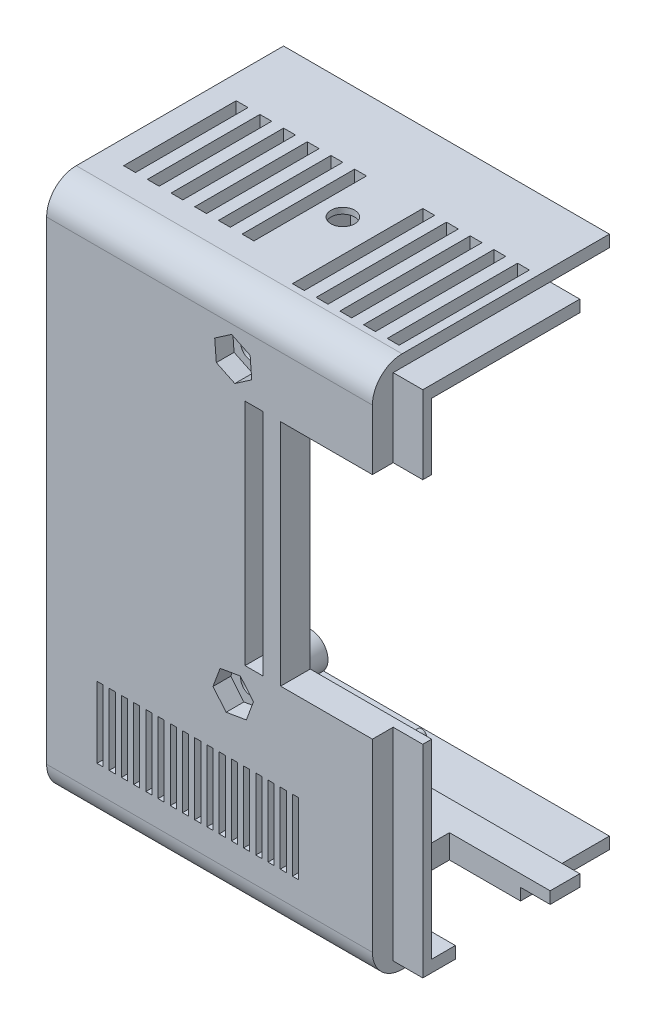
SolidWorks part; units mm, degrees
material "ABS"
ref_plane "Front Plane" through (0, 0, 0) normal (0, 0, 1) x (1, 0, 0)
ref_plane "Top Plane" through (0, 0, 0) normal (0, 1, 0) x (1, 0, 0)
ref_plane "Right Plane" through (0, 0, 0) normal (1, 0, 0) x (0, 0, -1)
sketch "Sketch1" plane through (0, 0, 0) normal (0, 0, 1) x (1, 0, 0)
  line L1 (50, 45) -> (-50, 45)
  line L2 (50, 45) -> (50, -45)
  line L3 (50, -45) -> (-50, -45)
  line L4 (-50, 45) -> (-50, -45)
  line L5 (0, -45) -> (0, 45) construction
  line L6 (50, 0) -> (-50, 0) construction
  line L7 (42.5, 28) -> (-42.5, 28)
  line L8 (42.5, 28) -> (42.5, -28)
  line L9 (42.5, -28) -> (-42.5, -28)
  line L10 (-42.5, 28) -> (-42.5, -28)
  line L11 (0, -28) -> (0, 28) construction
  line L12 (42.5, 0) -> (-42.5, 0) construction
  line L14 (0, 45) -> (0, -45)
  line L17 (0, 45) -> (60, 45)
  line L18 (0, 45) -> (0, -45)
  line L19 (0, -45) -> (60, -45)
  line L20 (60, 45) -> (60, -45)
  circle A0 centre (39.5, 35) radius 1.75
  circle A1 centre (39.5, -14) radius 1.75
  circle A2 centre (-18.5, 35) radius 1.75
  circle A3 centre (-18.5, -14) radius 1.75
  point P0 (0, 0)
  point P4 (0, 0)
  dimension "D5" = 3
  dimension "D6" = 10
  dimension "D7" = 90
  dimension "D9" = 49
  dimension "D10" = 10
  dimension "D11" = 24
  dimension "D12" = 49
  dimension "D13" = 110
  dimension "D14" = 58
  dimension "D15" = 24
  dimension "D16" = 3.5
  dimension "D1" = 100
  dimension "D2" = 60
  dimension "D3" = 85
  dimension "D4" = 56
  dimension "D8" = 3
extrude "Boss-Extrude1" add sketch "Sketch1" along normal blind 5 contours L7 L10 L9 L8 A3 A2 A1 A0 | L14 L1 L4 L3 L9 L10 L7 | L17 L20 L19 L4 | L14 L7 L10 L9 A3 A2 | L1 L14 L7 L8 L9 L3 L2 | L20 L17 L2 L19
sketch "Sketch2" plane through (0, 0, 0) normal (0, 0, -1) x (-1, 0, 0)
  circle A0 centre (-39.5, 35) radius 3
  circle A1 centre (-39.5, -14) radius 3
  circle A2 centre (18.5, -14) radius 3
  circle A3 centre (18.5, 35) radius 3
  dimension "D1" = 6
extrude "Boss-Extrude2" add sketch "Sketch2" along normal blind 8
sketch "Sketch3" plane through (0, 0, -8) normal (0, 0, -1) x (-1, 0, 0)
  circle A0 centre (-39.5, 35) radius 1.5
  circle A1 centre (18.5, 35) radius 1.5
  circle A2 centre (18.5, -14) radius 1.5
  circle A3 centre (-39.5, -14) radius 1.5
  dimension "D1" = 3
extrude "Cut-Extrude1" cut sketch "Sketch3" against normal up to next
sketch "Sketch4" plane through (0, 0, 5) normal (0, 0, 1) x (1, 0, 0)
  line L1 (-21.3541, 33.0369) -> (-18.2269, 31.5467)
  line L2 (-18.2269, 31.5467) -> (-15.3728, 33.5098)
  line L3 (-15.3728, 33.5098) -> (-15.6459, 36.9631)
  line L4 (-15.6459, 36.9631) -> (-18.7731, 38.4533)
  line L5 (-18.7731, 38.4533) -> (-21.6272, 36.4902)
  line L6 (-21.6272, 36.4902) -> (-21.3541, 33.0369)
  line L7 (38.5389, 31.6719) -> (41.9017, 32.5036)
  line L8 (41.9017, 32.5036) -> (42.8628, 35.8317)
  line L9 (42.8628, 35.8317) -> (40.4611, 38.3281)
  line L10 (40.4611, 38.3281) -> (37.0983, 37.4964)
  line L11 (37.0983, 37.4964) -> (36.1372, 34.1683)
  line L12 (36.1372, 34.1683) -> (38.5389, 31.6719)
  line L13 (38.2358, -17.2252) -> (41.661, -16.7074)
  line L14 (41.661, -16.7074) -> (42.9252, -13.4822)
  line L15 (42.9252, -13.4822) -> (40.7642, -10.7748)
  line L16 (40.7642, -10.7748) -> (37.339, -11.2926)
  line L17 (37.339, -11.2926) -> (36.0748, -14.5178)
  line L18 (36.0748, -14.5178) -> (38.2358, -17.2252)
  line L19 (-19.7009, -17.2493) -> (-16.2865, -16.6647)
  line L20 (-16.2865, -16.6647) -> (-15.0856, -13.4154)
  line L21 (-15.0856, -13.4154) -> (-17.2991, -10.7507)
  line L22 (-17.2991, -10.7507) -> (-20.7135, -11.3353)
  line L23 (-20.7135, -11.3353) -> (-21.9144, -14.5846)
  line L24 (-21.9144, -14.5846) -> (-19.7009, -17.2493)
  circle A0 centre (-18.5, 35) radius 3 construction
  circle A1 centre (39.5, 35) radius 3 construction
  circle A2 centre (39.5, -14) radius 3 construction
  circle A3 centre (-18.5, -14) radius 3 construction
  dimension "D1" = 6
extrude "Cut-Extrude2" cut sketch "Sketch4" against normal blind 3
sketch "Sketch5" plane through (0, 0, 0) normal (0, 0, -1) x (-1, 0, 0)
  line L0 (-60, -45) -> (50, -45) construction
  line L1 (-60, 45) -> (-55, 45)
  line L2 (-60, 45) -> (-60, -45)
  line L3 (-60, -45) -> (-55, -45)
  line L4 (-55, 45) -> (-55, -45)
  dimension "D1" = 5
extrude "Boss-Extrude3" add sketch "Sketch5" along normal blind 35
sketch "Sketch6" plane through (55, 0, 0) normal (-1, 0, 0) x (0, 0, 1)
  line L1 (-35, 45) -> (0, 45)
  line L2 (-35, 45) -> (-35, -45)
  line L3 (-35, -45) -> (0, -45)
  line L4 (0, 45) -> (0, -45)
  line L5 (-32, 0) -> (0, 0)
  line L6 (-19.5, 10.5) -> (-32, 10.5)
  line L7 (-19.5, 10.5) -> (-19.5, -10.5)
  line L8 (-19.5, -10.5) -> (-32, -10.5)
  line L9 (-32, 10.5) -> (-32, -10.5)
  line L10 (-25.75, -10.5) -> (-25.75, 10.5) construction
  line L11 (-19.5, 0) -> (-32, 0) construction
  line L16 (-32, -5) -> (-32, 5) construction
  line L17 (-13, 0) -> (-32, 0) construction
  line L18 (-15, 4) -> (-24, 4)
  line L19 (-15, 4) -> (-15, -4)
  line L20 (-15, -4) -> (-24, -4)
  line L21 (-24, 4) -> (-24, -4)
  line L22 (-19.5, -4) -> (-19.5, 4) construction
  line L23 (-15, 0) -> (-24, 0) construction
  circle A0 centre (-32, 10.5) radius 1.75
  circle A1 centre (-19.5, 10.5) radius 1.75
  circle A2 centre (-32, -10.5) radius 1.75
  circle A3 centre (-19.5, -10.5) radius 1.75
  point P9 (-25.75, 0)
  dimension "D4" = 3.5
  dimension "D1" = 12.5
  dimension "D2" = 21
  dimension "D3" = 3
  dimension "D5" = 8
  dimension "D6" = 9
extrude "Cut-Extrude3" cut sketch "Sketch6" against normal up to next contours L20 L19 L5 L7 | L19 L18 L7 L5 | L18 L21 L5 L7 | L5 L21 L20 L7 | A2 | A0 | A1 | A3
sketch "Sketch7" plane through (55, 0, 0) normal (-1, 0, 0) x (0, 0, 1)
  circle A0 centre (-19.5, 10.5) radius 2.25
  circle A1 centre (-19.5, -10.5) radius 2.25
  circle A2 centre (-32, -10.5) radius 2.25
  circle A3 centre (-32, 10.5) radius 2.25
  dimension "D1" = 4.5
extrude "Boss-Extrude4" add sketch "Sketch7" along normal blind 2
sketch "Sketch8" plane through (53, 0, 0) normal (-1, 0, 0) x (0, 0, 1)
  circle A0 centre (-32, 10.5) radius 1.5
  circle A1 centre (-19.5, 10.5) radius 1.5
  circle A2 centre (-19.5, -10.5) radius 1.5
  circle A3 centre (-32, -10.5) radius 1.5
  dimension "D1" = 3
extrude "Cut-Extrude4" cut sketch "Sketch8" against normal up to next
sketch "Sketch9" plane through (0, 0, 0) normal (0, 0, -1) x (-1, 0, 0)
  line L0 (50, 45) -> (50, -45) construction
  line L1 (-55, 45) -> (50, 45)
  line L2 (-55, 45) -> (-55, 41)
  line L3 (-55, 41) -> (50, 41)
  line L4 (50, 45) -> (50, 41)
  line L6 (-55, -45) -> (50, -45)
  line L7 (-55, -45) -> (-55, -41)
  line L8 (-55, -41) -> (50, -41)
  line L9 (50, -45) -> (50, -41)
  dimension "D1" = 4
  dimension "D2" = 4
extrude "Boss-Extrude5" add sketch "Sketch9" along normal blind 35
sketch "Sketch13" plane through (0, -41, 0) normal (0, 1, 0) x (1, 0, 0)
  line L0 (55, 0) -> (55, 35)
  line L1 (43, 0) -> (43, 35)
  line L3 (-50, 0) -> (55, 0) construction
  line L4 (-50, 35) -> (55, 35) construction
  line L5 (-7, 4) -> (43, 4)
  line L6 (-7, 20) -> (43, 20)
  line L7 (-7, 0) -> (-7, 35)
  dimension "D1" = 12
  dimension "D2" = 50
  dimension "D3" = 4
  dimension "D4" = 20
extrude "Cut-Extrude7" cut sketch "Sketch13" against normal up to next
sketch "Sketch15" plane through (0, 0, 5) normal (0, 0, 1) x (1, 0, 0)
  line L0 (-18.5, 35) -> (-18.5, -14)
  line L1 (39.5, 35) -> (39.5, -14)
  line L2 (-18.5, 10.5) -> (39.5, 10.5)
  line L3 (-13.5, 29.8339) -> (-13.5, -8.8339)
  line L4 (37.5, 29.8339) -> (-16.5, 29.8339)
  line L5 (37.5, 29.8339) -> (37.5, -8.8339)
  line L6 (37.5, -8.8339) -> (-16.5, -8.8339)
  line L7 (-16.5, 29.8339) -> (-16.5, -8.8339)
  line L8 (10.5, -8.8339) -> (10.5, 29.8339) construction
  line L9 (37.5, 10.5) -> (-16.5, 10.5) construction
  line L10 (-10.5, -8.8339) -> (-10.5, 29.8339)
  line L11 (-7.5, -8.8339) -> (-7.5, 29.8339)
  line L12 (-4.5, -8.8339) -> (-4.5, 29.8339)
  line L13 (-1.5, -8.8339) -> (-1.5, 29.8339)
  line L14 (1.5, 29.8339) -> (1.5, -8.8339)
  line L15 (4.5, -11.8339) -> (4.5, 29.8339)
  line L16 (7.5, -8.8339) -> (7.5, 29.8339)
  line L17 (10.5, -8.8339) -> (10.5, 29.8339)
  line L18 (13.5, -8.8339) -> (13.5, 29.8339)
  line L19 (16.5, -11.8339) -> (16.5, 29.8339)
  line L20 (19.5, 29.8339) -> (19.5, -8.8339)
  line L21 (22.5, -8.8339) -> (22.5, 29.8339)
  line L22 (25.5, -8.8339) -> (25.5, 29.8339)
  line L23 (28.5, -8.8339) -> (28.5, 29.8339)
  line L24 (31.5, -8.8339) -> (31.5, 29.8339)
  line L25 (34.5, 29.8339) -> (34.5, -8.8339)
  point P10 (10.5, 10.5)
  dimension "D1" = 2
  dimension "D2" = 3
  dimension "D3" = 38.6677
  dimension "D4" = 3
  dimension "D5" = 3
  dimension "D6" = 3
  dimension "D7" = 3
  dimension "D8" = 3
  dimension "D9" = 3
  dimension "D10" = 3
  dimension "D11" = 3
extrude "Cut-Extrude9" cut sketch "Sketch15" against normal blind 10 contours L2 L7 L6 L3 | L6 L11 L2 L10 | L6 L13 L2 L12 | L6 L15 L2 L14 | L6 L17 L2 L16 | L6 L19 L2 L18 | L6 L21 L2 L20 | L6 L23 L2 L22 | L25 L2 L24 L6 | L4 L7 L2 L3 | L2 L11 L4 L10 | L2 L13 L4 L12 | L2 L15 L4 L14 | L2 L17 L4 L16 | L2 L19 L4 L18 | L2 L21 L4 L20 | L2 L23 L4 L22 | L25 L4 L24 L2
sketch "Sketch18" plane through (0, 0, 0) normal (0, 0, -1) x (-1, 0, 0)
  line L1 (-55, 41) -> (50, 41) construction
  line L2 (-55, 41) -> (-55, -41)
  line L3 (50, -41) -> (-55, -41) construction
  line L5 (50, 41) -> (-55, 41)
  line L6 (50, 41) -> (50, -41)
  line L7 (50, -41) -> (-55, -41)
  line L8 (-55, 41) -> (-55, -41)
  circle A0 centre (-49, 35) radius 5
  circle A1 centre (-49, -35) radius 5
  dimension "D1" = 10
  dimension "D2" = 10
  dimension "D3" = 6
  dimension "D4" = 6
  dimension "D5" = 6
  dimension "D6" = 6
  dimension "D7" = 105
  dimension "D8" = 82
extrude "Boss-Extrude7" add sketch "Sketch18" along normal blind 35 contours A1 | A0
sketch "Sketch20" plane through (55, 0, 0) normal (-1, 0, 0) x (0, 0, 1)
  line L0 (0, -41) -> (0, 41) construction
  circle A0 centre (-19, -22.8922) radius 3
  circle A1 centre (-9, -22.8922) radius 3
  dimension "D1" = 6
  dimension "D2" = 19
  dimension "D3" = 6
  dimension "D4" = 10
extrude "Cut-Extrude10" cut sketch "Sketch20" against normal up to next
sketch "Sketch21" plane through (0, 0, -35) normal (0, 0, -1) x (-1, 0, 0)
  circle A0 centre (-49, 35) radius 1.75
  circle A1 centre (-49, -35) radius 1.75
  dimension "D1" = 3.5
extrude "Cut-Extrude11" cut sketch "Sketch21" against normal up to next
sketch "Sketch22" plane through (0, 0, 5) normal (0, 0, 1) x (1, 0, 0)
  line L1 (46.9194, 38.1232) -> (45.2549, 34.7597)
  line L2 (45.2549, 34.7597) -> (47.3356, 31.6365)
  line L3 (47.3356, 31.6365) -> (51.0806, 31.8768)
  line L4 (51.0806, 31.8768) -> (52.7451, 35.2403)
  line L5 (52.7451, 35.2403) -> (50.6644, 38.3635)
  line L6 (50.6644, 38.3635) -> (46.9194, 38.1232)
  line L7 (52.7528, -35) -> (50.8764, -31.75)
  line L8 (50.8764, -31.75) -> (47.1236, -31.75)
  line L9 (47.1236, -31.75) -> (45.2472, -35)
  line L10 (45.2472, -35) -> (47.1236, -38.25)
  line L11 (47.1236, -38.25) -> (50.8764, -38.25)
  line L12 (50.8764, -38.25) -> (52.7528, -35)
  circle A0 centre (49, 35) radius 3.25 construction
  circle A1 centre (49, -35) radius 3.25 construction
  dimension "D1" = 6.5
  dimension "D2" = 6.5
extrude "Cut-Extrude12" cut sketch "Sketch22" against normal blind 30
sketch "Sketch23" plane through (0, -41, 0) normal (0, 1, 0) x (1, 0, 0)
  line L0 (-50, 0) -> (-50, 35)
  line L8 (-50, 35) -> (55, 35)
  line L9 (55, 0) -> (55, 35)
  circle A0 centre (-20, 15) radius 2
  dimension "D1" = 4
  dimension "D3" = 30
  dimension "D2" = 20
extrude "Cut-Extrude13" cut sketch "Sketch23" against normal up to next and the other way up to next contours A0
sketch "Sketch24" plane through (0, 41, 0) normal (0, -1, 0) x (-1, 0, 0)
  line L1 (16.5359, 15) -> (18.2679, 12)
  line L2 (18.2679, 12) -> (21.7321, 12)
  line L3 (21.7321, 12) -> (23.4641, 15)
  line L4 (23.4641, 15) -> (21.7321, 18)
  line L5 (21.7321, 18) -> (18.2679, 18)
  line L6 (18.2679, 18) -> (16.5359, 15)
  circle A0 centre (20, 15) radius 3 construction
  dimension "D1" = 6
extrude "Cut-Extrude14" cut sketch "Sketch24" against normal blind 3
sketch "Sketch25" plane through (0, -41, 0) normal (0, 1, 0) x (1, 0, 0)
  line L1 (-23.4521, 14.7114) -> (-21.4761, 11.8661)
  line L2 (-21.4761, 11.8661) -> (-18.024, 12.1547)
  line L3 (-18.024, 12.1547) -> (-16.5479, 15.2886)
  line L4 (-16.5479, 15.2886) -> (-18.5239, 18.1339)
  line L5 (-18.5239, 18.1339) -> (-21.976, 17.8453)
  line L6 (-21.976, 17.8453) -> (-23.4521, 14.7114)
  circle A0 centre (-20, 15) radius 3 construction
  dimension "D1" = 6
extrude "Cut-Extrude15" cut sketch "Sketch25" against normal blind 3
sketch "Sketch27" plane through (0, 0, 0) normal (0, 0, -1) x (-1, 0, 0)
  line L0 (50, -41) -> (-55, -41) construction
  line L1 (-2.5, -41) -> (45.32, -41)
  line L5 (50, 41) -> (50, -41) construction
  line L7 (45.32, -22) -> (4.68, -22)
  line L8 (45.32, -22) -> (45.32, -37.24)
  line L9 (45.32, -37.24) -> (4.68, -37.24)
  line L10 (4.68, -22) -> (4.68, -37.24)
  line L11 (25, -37.24) -> (25, -22) construction
  line L12 (45.32, -29.62) -> (4.68, -29.62) construction
  circle A0 centre (4.68, -22) radius 2.5
  circle A1 centre (4.68, -37.24) radius 2.5
  circle A2 centre (45.32, -37.24) radius 2.5
  circle A3 centre (45.32, -22) radius 2.5
  point P8 (25, -29.62)
  dimension "D6" = 5
  dimension "D1" = 40.64
  dimension "D2" = 15.24
  dimension "D3" = 11.38
  dimension "D7" = 25
extrude "Boss-Extrude9" add sketch "Sketch27" along normal blind 10 contours A0 | A1 | A2 | A3
sketch "Sketch28" plane through (0, 0, -10) normal (0, 0, -1) x (-1, 0, 0)
  circle A0 centre (4.68, -22) radius 0.85
  circle A1 centre (4.68, -37.24) radius 0.85
  circle A2 centre (45.32, -37.24) radius 0.85
  circle A3 centre (45.32, -22) radius 0.85
  dimension "D1" = 1.7
extrude "Boss-Extrude10" add sketch "Sketch28" along normal blind 3
sketch "Sketch29" plane through (0, 0, 0) normal (0, 0, -1) x (-1, 0, 0)
  line L0 (50, -41) -> (-55, -41) construction
  line L1 (50, 41) -> (48, 41)
  line L2 (50, 41) -> (50, -41)
  line L3 (50, -41) -> (48, -41)
  line L4 (48, 41) -> (48, -41)
  dimension "D1" = 2
extrude "Boss-Extrude11" add sketch "Sketch29" along normal blind 10
sketch "Sketch30" plane through (0, 0, -35) normal (0, 0, -1) x (-1, 0, 0)
  line L0 (50, 41) -> (50, 45) construction
  line L1 (50, 41) -> (-55, 41)
  line L2 (50, 41) -> (50, -41)
  line L3 (50, -41) -> (-55, -41)
  line L4 (-55, 41) -> (-55, -41)
  line L5 (50, 43) -> (-57, 43)
  line L6 (50, 43) -> (50, -43)
  line L7 (50, -43) -> (-57, -43)
  line L8 (-57, 43) -> (-57, -43)
  line L10 (-57, 15) -> (-55, 15)
  line L12 (-57, -15) -> (-55, -15)
  line L13 (-55, 15) -> (-55, -15)
  line L14 (-57, -15) -> (-57, 15) construction
  point P12 (-57, 0)
  line M5 (50, -45) -> (50, -41)
  line M6 (50, -41) -> (-55, -41)
  line M7 (-55, -41) -> (-55, 41)
  line M8 (-55, 41) -> (50, 41)
  line M9 (50, 41) -> (50, 45)
  dimension "D1" = 86
  dimension "D2" = 107
extrude "Cut-Extrude16" cut sketch "Sketch30" against normal blind 10 contours L5 L8 L7 M5 M6 M7 M8 M9 | L8 L10 L4 L5 M8 M9
fillet "Fillet3" radius 5 2 edges at (60, -45, -15) (60, 45, -15)
fillet "Fillet4" radius 5 5 edges at (58.5355, -43.5355, 5) (60, 0, 5) (58.5355, 43.5355, 5) (2.5, -45, 5) (2.5, 45, 5)
sketch "Sketch32" plane through (0, 0, 5) normal (0, 0, 1) x (1, 0, 0)
  line L1 (-7.5, 29.8339) -> (1.5, 29.8339)
  line L2 (-7.5, 29.8339) -> (-7.5, -8.8339)
  line L3 (-7.5, -8.8339) -> (1.5, -8.8339)
  line L4 (1.5, 29.8339) -> (1.5, -8.8339)
  line L5 (-7.5, 29.8339) -> (7.5, 29.8339)
  line L6 (-7.5, 29.8339) -> (-7.5, -8.8339)
  line L7 (-7.5, -8.8339) -> (7.5, -8.8339)
  line L8 (7.5, 29.8339) -> (7.5, -8.8339)
extrude "Cut-Extrude17" cut sketch "Sketch32" against normal blind 35 contours L4 L1 L2 L3 | L8 L5 L4 L7
chamfer "Chamfer1" distance 3 angle 60 4 edges at (60, 0, -15) (60, 4, -19.5) (60, 0, -24) (60, -4, -19.5)
sketch "Sketch34" plane through (0, 0, -10) normal (0, 0, -1) x (-1, 0, 0)
  line L6 (50, 41) -> (48, 41)
  line L7 (50, 41) -> (50, -41)
  line L8 (50, -41) -> (48, -41)
  line L9 (48, 41) -> (48, -41)
extrude "Boss-Extrude12" add sketch "Sketch34" along normal up to surface (25 mm away) up to face at (26.4336, 0, -35)
sketch "Sketch35" plane through (0, 0, -35) normal (0, 0, -1) x (-1, 0, 0)
  line L0 (48, -41) -> (50, -41) construction
  line L1 (48, 41) -> (49, 41)
  line L2 (48, 41) -> (48, -41)
  line L3 (48, -41) -> (49, -41)
  line L4 (49, 41) -> (49, -41)
extrude "Cut-Extrude18" cut sketch "Sketch35" against normal blind 10
sketch "Sketch36" plane through (-48, 0, 0) normal (1, 0, 0) x (0, 0, -1)
  line L0 (25, 0) -> (0, 0)
  line L1 (0, 41) -> (25, 41)
  line L2 (0, 41) -> (0, -41)
  line L3 (0, -41) -> (25, -41)
  line L4 (25, 41) -> (25, -41)
  line L6 (22.5, 39) -> (2.5, 39)
  line L7 (22.5, 39) -> (22.5, -39)
  line L8 (22.5, -39) -> (2.5, -39)
  line L9 (2.5, 39) -> (2.5, -39)
  line L10 (12.5, -39) -> (12.5, 39) construction
  line L11 (22.5, 0) -> (2.5, 0) construction
  point P8 (12.5, 0)
  dimension "D1" = 78
  dimension "D2" = 20
extrude "Cut-Extrude19" cut sketch "Sketch36" against normal up to next contours L0 L9 L8 L7 | L6 L9 L0 L7
sketch "Sketch37" plane through (0, 0, 0) normal (0, 0, -1) x (-1, 0, 0)
  text T0 "J T M T R" font "Impact" height in points 28
extrude "Cut-Extrude21" cut sketch "Sketch37" against normal up to next
sketch "Sketch38" plane through (0, 0, 0) normal (0, 0, -1) x (-1, 0, 0)
  line L0 (25, -22) -> (25, -37.24)
  line L1 (4.68, -22) -> (45.32, -22)
  line L2 (4.68, -22) -> (4.68, -37.24)
  line L3 (4.68, -37.24) -> (45.32, -37.24)
  line L4 (45.32, -22) -> (45.32, -37.24)
  line L5 (8.5, -23.62) -> (8.5, -35.62)
  line L6 (42.5, -23.62) -> (7.5, -23.62)
  line L7 (42.5, -23.62) -> (42.5, -35.62)
  line L8 (42.5, -35.62) -> (7.5, -35.62)
  line L9 (7.5, -23.62) -> (7.5, -35.62)
  line L10 (25, -35.62) -> (25, -23.62) construction
  line L11 (42.5, -29.62) -> (7.5, -29.62) construction
  line L12 (9.5312, -23.62) -> (9.5312, -35.62)
  line L13 (10.5625, -23.62) -> (10.5625, -35.62)
  line L14 (11.5937, -23.62) -> (11.5937, -35.62)
  line L15 (12.625, -23.62) -> (12.625, -35.62)
  line L16 (13.6562, -23.62) -> (13.6562, -35.62)
  line L17 (14.6875, -23.62) -> (14.6875, -35.62)
  line L18 (15.7187, -23.62) -> (15.7187, -35.62)
  line L19 (16.75, -23.62) -> (16.75, -35.62)
  line L20 (17.7812, -23.62) -> (17.7812, -35.62)
  line L21 (18.8125, -23.62) -> (18.8125, -35.62)
  line L22 (19.8437, -23.62) -> (19.8438, -35.62)
  line L23 (20.875, -23.62) -> (20.875, -35.62)
  line L24 (21.9062, -23.62) -> (21.9062, -35.62)
  line L25 (22.9375, -23.62) -> (22.9375, -35.62)
  line L26 (23.9687, -23.62) -> (23.9687, -35.62)
  line L27 (25, -23.62) -> (25, -35.62)
  line L28 (26.0312, -23.62) -> (26.0312, -35.62)
  line L29 (27.0625, -23.62) -> (27.0625, -35.62)
  line L30 (28.0937, -23.62) -> (28.0938, -35.62)
  line L31 (29.125, -23.62) -> (29.125, -35.62)
  line L32 (30.1562, -23.62) -> (30.1563, -35.62)
  line L33 (31.1875, -23.62) -> (31.1875, -35.62)
  line L34 (32.2188, -23.62) -> (32.2188, -35.62)
  line L35 (33.25, -23.62) -> (33.25, -35.62)
  line L36 (34.2812, -23.62) -> (34.2812, -35.62)
  line L37 (35.3125, -23.62) -> (35.3125, -35.62)
  line L38 (36.3438, -23.62) -> (36.3438, -35.62)
  line L39 (37.375, -23.62) -> (37.375, -35.62)
  line L40 (38.4062, -23.62) -> (38.4062, -35.62)
  line L41 (39.4375, -23.62) -> (39.4375, -35.62)
  line L42 (40.4688, -23.62) -> (40.4688, -35.62)
  line L43 (41.5, -23.62) -> (41.5, -35.62)
  line L44 (42.5312, -23.62) -> (42.5312, -35.62)
  point P8 (25, -29.62)
  dimension "D1" = 12
  dimension "D2" = 35
  dimension "D3" = 1
  dimension "D4" = 34
extrude "Cut-Extrude22" cut sketch "Sketch38" against normal up to next (5 mm away) contours L6 L9 L8 L5 | L13 L6 L12 L8 | L15 L6 L14 L8 | L17 L6 L16 L8 | L19 L6 L18 L8 | L21 L6 L20 L8 | L23 L6 L22 L8 | L25 L6 L24 L8 | L6 L26 L8 L0 | L29 L6 L28 L8 | L31 L6 L30 L8 | L33 L6 L32 L8 | L35 L6 L34 L8 | L37 L6 L36 L8 | L39 L6 L38 L8 | L41 L6 L40 L8 | L43 L6 L42 L8
sketch "Sketch40" plane through (0, 41, 0) normal (0, -1, 0) x (1, 0, 0)
  line L0 (3.5, -25) -> (3.5, 0)
  line L1 (55, 0) -> (-48, 0)
  line L2 (55, 0) -> (55, -25)
  line L3 (55, -25) -> (-48, -25)
  line L4 (-48, 0) -> (-48, -25)
  line L5 (5.5, -25) -> (5.5, 0)
  line L6 (3.5, -25) -> (41.5, -25)
  line L7 (3.5, -25) -> (3.5, 0)
  line L8 (3.5, 0) -> (41.5, 0)
  line L9 (41.5, -25) -> (41.5, 0)
  line L10 (7.5, -25) -> (7.5, 0)
  line L11 (9.5, -25) -> (9.5, 0)
  line L12 (11.5, -25) -> (11.5, 0)
  line L13 (13.5, -25) -> (13.5, 0)
  line L14 (15.5, -25) -> (15.5, 0)
  line L15 (17.5, -25) -> (17.5, 0)
  line L16 (19.5, -25) -> (19.5, 0)
  line L17 (21.5, -25) -> (21.5, 0)
  line L18 (23.5, -25) -> (23.5, 0)
  line L19 (25.5, -25) -> (25.5, 0)
  line L20 (27.5, -25) -> (27.5, 0)
  line L21 (29.5, -25) -> (29.5, 0)
  line L22 (31.5, -25) -> (31.5, 0)
  line L23 (33.5, -25) -> (33.5, 0)
  line L24 (35.5, -25) -> (35.5, 0)
  line L25 (37.5, -25) -> (37.5, 0)
  line L26 (39.5, -25) -> (39.5, 0)
  line L27 (3.5, -25) -> (3.5, 0)
  line L28 (1.5, -25) -> (1.5, 0)
  line L29 (-0.5, -25) -> (-0.5, 0)
  line L30 (-2.5, -25) -> (-2.5, 0)
  line L31 (-4.5, -25) -> (-4.5, 0)
  line L32 (-6.5, -25) -> (-6.5, 0)
  line L33 (-8.5, -25) -> (-8.5, 0)
  line L34 (-10.5, -25) -> (-10.5, 0)
  line L35 (-12.5, -25) -> (-12.5, 0)
  line L36 (-14.5, -25) -> (-14.5, 0)
  line L37 (41.5, -23) -> (-14.5, -23)
  line L38 (43.5, -25) -> (43.5, 0)
  line L39 (41.5, -23) -> (43.5, -23)
  line L41 (43.5, -1) -> (-14.5, -1)
  dimension "D1" = 103
  dimension "D2" = 25
  dimension "D3" = 38
  dimension "D4" = 2
  dimension "D7" = 2
  dimension "D8" = 2
  dimension "D9" = 1
  dimension "D5" = 18
  dimension "D6" = 11
extrude "Cut-Extrude26" cut sketch "Sketch40" against normal blind 10 contours L35 L41 L36 L37 | L33 L41 L34 L37 | L31 L41 L32 L37 | L29 L41 L30 L37 | L27 L41 L28 L37 | L10 L41 L5 L37 | L12 L41 L11 L37 | L14 L41 L13 L37 | L16 L41 L15 L37 | L18 L41 L17 L37 | L20 L41 L19 L37 | L22 L41 L21 L37 | L24 L41 L23 L37 | L26 L41 L25 L37 | L38 L41 L9 L39
sketch "Sketch41" plane through (60, 0, 0) normal (1, 0, 0) x (0, 0, -1)
  line L1 (9.2039, 27.4935) -> (6, 28.583)
  line L2 (6, 28.583) -> (6, 29.9666)
  line L7 (6, 29.9666) -> (9.2039, 31.0579)
  line L10 (9.2039, 31.0579) -> (9.2039, 29.6449)
  line L11 (9.2039, 29.6449) -> (8.1414, 29.2764)
  line L12 (8.1414, 29.2764) -> (9.2039, 28.9172)
  line L13 (9.2039, 28.9172) -> (9.2039, 27.4935)
  line L14 (6, 24.8903) -> (6, 26.3321)
  line L15 (6, 26.3321) -> (8.8835, 26.3321)
  line L16 (8.8835, 26.3321) -> (9.284, 24.8903)
  line L17 (9.284, 24.8903) -> (6, 24.8903)
extrude "Cut-Extrude30" cut sketch "Sketch41" against normal up to next (5 mm away)
sketch "Sketch44" plane through (0, 0, 0) normal (0, 0, -1) x (-1, 0, 0)
  line L0 (-5, 45) -> (-5, -45)
  line L1 (50, -45) -> (-60, -45)
  line L2 (50, -45) -> (50, 45)
  line L3 (50, 45) -> (-60, 45)
  line L4 (-60, -45) -> (-60, 45)
extrude "Cut-Extrude31" cut sketch "Sketch44" against normal through all both and the other way through all contours L4 L1 L0 L3
sketch "Sketch45" plane through (5, 0, 0) normal (1, 0, 0) x (0, 0, -1)
  line L0 (25, 41) -> (0, 41)
  line L1 (25, 43) -> (-1.5, 43)
  line L2 (25, 43) -> (25, -43)
  line L3 (25, -43) -> (-1.5, -43)
  line L4 (-1.5, 43) -> (-1.5, -43)
  line L5 (0, 41) -> (0, 29.8339)
  line L6 (0, 29.8339) -> (-1.5, 29.8339)
  line L7 (-5, 29.8339) -> (0, 29.8339) construction
  line L8 (-1.5, -8.8339) -> (0, -8.8339)
  line L9 (0, -8.8339) -> (0, -41)
  line L10 (0, -41) -> (4, -41)
  line L11 (4, -41) -> (4, -43)
  line L12 (4, -45) -> (4, -41) construction
  line L13 (20, -43) -> (20, -41)
  line L14 (20, -45) -> (20, -41) construction
  line L15 (20, -41) -> (25, -41)
  line L16 (25, -41) -> (25, -43)
  line M3 (-5, 29.8339) -> (0, 29.8339)
  line M4 (0, 29.8339) -> (0, 41)
  line M5 (0, 41) -> (25, 41)
  line M6 (25, 41) -> (25, 43)
  dimension "D1" = 26.5
extrude "Boss-Extrude13" add sketch "Sketch45" along normal blind 5 contours L1 L4 M3 M4 M5 M6 | L15 L13 L3 L2 | L11 L10 L9 L8 L4 L3
sketch "Sketch46" plane through (-50, 0, 0) normal (-1, 0, 0) x (0, 0, 1)
  line L1 (-35, 41) -> (-2.5, 41)
  line L2 (-35, 41) -> (-35, -41)
  line L3 (-35, -41) -> (-2.5, -41)
  line L4 (-2.5, 41) -> (-2.5, -41)
  dimension "D1" = 32.5
  dimension "D2" = 82
extrude "Cut-Extrude32" cut sketch "Sketch46" against normal up to next
sketch "Sketch48" plane through (0, 0, -2.5) normal (0, 0, -1) x (-1, 0, 0)
  line L0 (48, 41) -> (48, -41) construction
  line L1 (50, 41) -> (48, 41)
  line L2 (50, 41) -> (50, 38)
  line L3 (50, 38) -> (48, 38)
  line L4 (48, 41) -> (48, 38)
  line L6 (50, -41) -> (48, -41)
  line L7 (50, -41) -> (50, -38)
  line L8 (50, -38) -> (48, -38)
  line L9 (48, -41) -> (48, -38)
  dimension "D1" = 3
  dimension "D2" = 3
extrude "Boss-Extrude14" add sketch "Sketch48" along normal up to surface (22.5 mm away) up to face at (-15, 42.2, -25)
sketch "Sketch49" plane through (0, 0, -2.5) normal (0, 0, -1) x (-1, 0, 0)
  line L1 (50, 38) -> (48, 38)
  line L2 (50, 38) -> (50, -38)
  line L3 (50, -38) -> (48, -38)
  line L4 (48, 38) -> (48, -38)
  dimension "D1" = 2
  dimension "D2" = 76
extrude "Boss-Extrude15" add sketch "Sketch49" along normal blind 4
sketch "Sketch50" plane through (0, 0, -25) normal (0, 0, -1) x (-1, 0, 0)
  line L0 (50, 43) -> (-5, 43) construction
  line L1 (48, 38) -> (49, 38)
  line L2 (48, 38) -> (48, 43)
  line L3 (48, 43) -> (49, 43)
  line L4 (49, 38) -> (49, 43)
  line L5 (-5, -45) -> (50, -45) construction
  line L6 (48, -38) -> (49, -38)
  line L7 (48, -38) -> (48, -45)
  line L8 (48, -45) -> (49, -45)
  line L9 (49, -38) -> (49, -45)
  dimension "D1" = 1
  dimension "D2" = 1
  dimension "D3" = 7
extrude "Boss-Extrude16" add sketch "Sketch50" along normal up to surface (10 mm away) up to face at (-22.5, 44, -35)
sketch "Sketch52" plane through (0, 41, 0) normal (0, -1, 0) x (1, 0, 0)
  line L0 (10, -4) -> (-48, -4)
  line L1 (-48, 0) -> (10, 0)
  line L2 (-48, 0) -> (-48, -25)
  line L3 (-48, -25) -> (10, -25)
  line L4 (10, 0) -> (10, -25)
  line L5 (8, -25) -> (8, -4)
  line L6 (6, -25) -> (6, -4)
  line L7 (4, -25) -> (4, -4)
  line L8 (2, -25) -> (2, -4)
  line L9 (0, -25) -> (0, -4)
  line L10 (-2, -25) -> (-2, -4)
  line L11 (-4, -25) -> (-4, -4)
  line L12 (-6, -25) -> (-6, -4)
  line L13 (-8, -25) -> (-8, -4)
  line L14 (-10, -25) -> (-10, -4)
  line L15 (-12, -25) -> (-12, -4)
  line L16 (-14, -25) -> (-14, -4)
  line L17 (-16, -25) -> (-16, -4)
  line L18 (-18, -25) -> (-18, -4)
  line L19 (-20, -25) -> (-20, -4)
  line L20 (-22, -25) -> (-22, -4)
  line L21 (-24, -25) -> (-24, -4)
  line L22 (-26, -25) -> (-26, -4)
  line L23 (-28, -25) -> (-28, -4)
  line L24 (-30, -25) -> (-30, -4)
  line L25 (-32, -25) -> (-32, -4)
  line L26 (-34, -25) -> (-34, -4)
  line L27 (-36, -25) -> (-36, -4)
  line L28 (-38, -25) -> (-38, -4)
  line L29 (-40, -25) -> (-40, -4)
  line L30 (-42, -25) -> (-42, -4)
  line L31 (-44, -25) -> (-44, -4)
  line L32 (-46, -25) -> (-46, -4)
  line L33 (-48, -23) -> (10, -23)
  dimension "D1" = 4
  dimension "D2" = 2
  dimension "D4" = 2
  dimension "D3" = 28
extrude "Cut-Extrude33" cut sketch "Sketch52" against normal up to next contours L32 L3 L31 L0 | L30 L3 L29 L0 | L28 L3 L27 L0 | L26 L3 L25 L0 | L24 L3 L23 L0 | L22 L3 L21 L0
sketch "Sketch53" plane through (0, -45, 0) normal (0, -1, 0) x (1, 0, 0)
  line L0 (-48, -23) -> (10, -23) construction
  line L1 (4, -25) -> (4, -4) construction
  line L2 (6, -25) -> (6, -4) construction
  line L3 (8, -25) -> (8, -4) construction
  line L4 (10, 0) -> (-48, 0)
  line L5 (10, -25) -> (10, 0)
  line L6 (-48, -25) -> (10, -25)
  line L7 (-48, 0) -> (-48, -25)
  line L8 (-50, 0) -> (-50, -35)
  line L9 (-50, -35) -> (5, -35)
  line L10 (5, -35) -> (5, -20)
  line L11 (5, -20) -> (-7, -20)
  line L12 (-7, -20) -> (-7, -4)
  line L13 (-7, -4) -> (5, -4)
  line L14 (5, -4) -> (5, 0)
  line L15 (5, 0) -> (-50, 0)
  line L16 (-50, 0) -> (-50, -35)
  line L17 (-50, -35) -> (5, -35)
  line L18 (5, -35) -> (5, -20)
  line L19 (5, -20) -> (-7, -20)
  line L20 (-7, -20) -> (-7, -4)
  line L21 (-7, -4) -> (5, -4)
  line L22 (5, -4) -> (5, 0)
  line L23 (5, 0) -> (-50, 0)
  line L24 (10, 0) -> (-48, 0)
  line L25 (10, -25) -> (10, 0)
  line L26 (-48, -25) -> (10, -25)
  line L27 (-48, 0) -> (-48, -25)
  line L28 (10, -4) -> (-48, -4) construction
  line L29 (-12, -25) -> (-12, -4) construction
  line L30 (-10, -25) -> (-10, -4) construction
  line L31 (-8, -25) -> (-8, -4) construction
  line L32 (-6, -25) -> (-6, -4) construction
  line L33 (-4, -25) -> (-4, -4) construction
  line L34 (-2, -25) -> (-2, -4) construction
  line L35 (0, -25) -> (0, -4) construction
  line L36 (2, -25) -> (2, -4) construction
  line L37 (-28, -25) -> (-28, -4) construction
  line L38 (-26, -25) -> (-26, -4) construction
  line L39 (-24, -25) -> (-24, -4) construction
  line L40 (-22, -25) -> (-22, -4) construction
  line L41 (-20, -25) -> (-20, -4) construction
  line L42 (-18, -25) -> (-18, -4) construction
  line L43 (-16, -25) -> (-16, -4) construction
  line L44 (-14, -25) -> (-14, -4) construction
  line L45 (-44, -25) -> (-44, -4) construction
  line L46 (-42, -25) -> (-42, -4) construction
  line L47 (-40, -25) -> (-40, -4) construction
  line L48 (-38, -25) -> (-38, -4) construction
  line L49 (-36, -25) -> (-36, -4) construction
  line L50 (-34, -25) -> (-34, -4) construction
  line L51 (-32, -25) -> (-32, -4) construction
  line L52 (-30, -25) -> (-30, -4) construction
  line L53 (-46, -25) -> (-46, -4) construction
  line L54 (-48, -23) -> (10, -23)
  line L55 (4, -25) -> (4, -4)
  line L56 (6, -25) -> (6, -4)
  line L57 (8, -25) -> (8, -4)
  line L58 (10, -4) -> (-48, -4)
  line L59 (-12, -25) -> (-12, -4)
  line L60 (-10, -25) -> (-10, -4)
  line L61 (-8, -25) -> (-8, -4)
  line L62 (-6, -25) -> (-6, -4)
  line L63 (-4, -25) -> (-4, -4)
  line L64 (-2, -25) -> (-2, -4)
  line L65 (0, -25) -> (0, -4)
  line L66 (2, -25) -> (2, -4)
  line L67 (-28, -25) -> (-28, -4)
  line L68 (-26, -25) -> (-26, -4)
  line L69 (-24, -25) -> (-24, -4)
  line L70 (-22, -25) -> (-22, -4)
  line L71 (-20, -25) -> (-20, -4)
  line L72 (-18, -25) -> (-18, -4)
  line L73 (-16, -25) -> (-16, -4)
  line L74 (-14, -25) -> (-14, -4)
  line L75 (-44, -25) -> (-44, -4)
  line L76 (-42, -25) -> (-42, -4)
  line L77 (-40, -25) -> (-40, -4)
  line L78 (-38, -25) -> (-38, -4)
  line L79 (-36, -25) -> (-36, -4)
  line L80 (-34, -25) -> (-34, -4)
  line L81 (-32, -25) -> (-32, -4)
  line L82 (-30, -25) -> (-30, -4)
  line L83 (-46, -25) -> (-46, -4)
  dimension "D1" = 0
  dimension "D2" = 0
extrude "Cut-Extrude34" cut sketch "Sketch53" against normal up to next contours L83 L54 L75 L58 | L54 L77 L58 L76 | L54 L79 L58 L78 | L54 L81 L58 L80 | L82 L54 L67 L58 | L54 L69 L58 L68
sketch "Sketch54" plane through (0, 0, -10) normal (0, 0, -1) x (-1, 0, 0)
  line L0 (45.32, -39.74) -> (45.32, -41)
  line L1 (48, -41) -> (-10, -41) construction
  line L2 (45.32, -41) -> (48, -41)
  line L3 (48, -41) -> (48, -37.24)
  line L4 (48, 38) -> (48, -38) construction
  line L5 (48, -37.24) -> (47.82, -37.24)
  line L6 (2.18, -37.24) -> (2.18, -41)
  line L7 (48, -41) -> (-10, -41) construction
  line L8 (2.18, -41) -> (7.18, -41)
  line L9 (7.18, -41) -> (7.18, -37.24)
  line L11 (45.32, -22) -> (48, -22)
  line L12 (45.32, -22) -> (45.32, -19.5)
  line L13 (45.32, -19.5) -> (48, -19.5)
  line L14 (48, -22) -> (48, -19.5)
  circle A0 centre (45.32, -37.24) radius 2.5 construction
  circle A1 centre (45.32, -37.24) radius 2.5 construction
  circle A2 centre (4.68, -37.24) radius 2.5 construction
  circle A3 centre (4.68, -37.24) radius 2.5 construction
  circle A4 centre (45.32, -37.24) radius 2.5
  circle A5 centre (4.68, -37.24) radius 2.5
extrude "Boss-Extrude17" add sketch "Sketch54" against normal up to surface (10 mm away) contours L11 L14 L13 L12 | A4 L0 L2 L3 L5 | A5 L6 L8 L9
